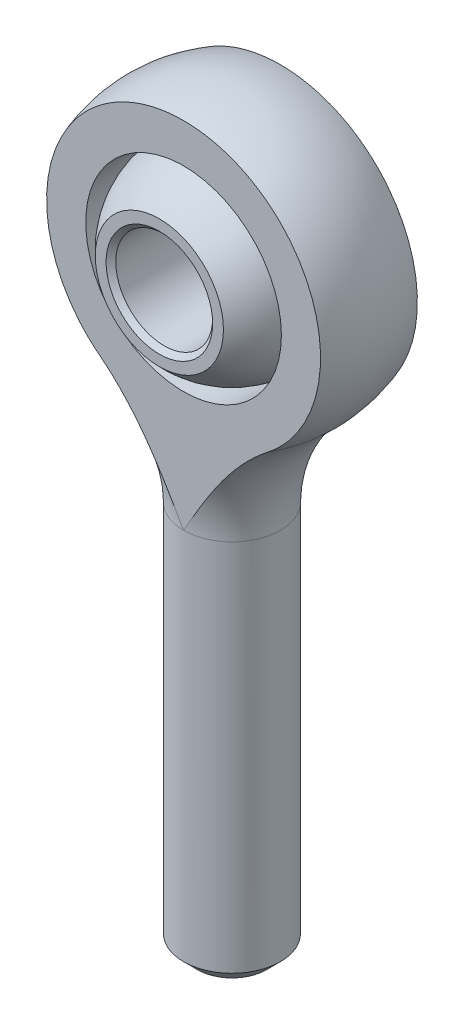
SolidWorks part; units mm, degrees
material "Cast Carbon Steel"
ref_plane "Front" through (0, 0, 0) normal (0, 0, 1) x (1, 0, 0)
ref_plane "Top" through (0, 0, 0) normal (0, 1, 0) x (1, 0, 0)
ref_plane "Right" through (0, 0, 0) normal (1, 0, 0) x (0, 0, -1)
sketch "Sketch1" plane through (0, 0, 0) normal (0, 0, 1) x (1, 0, 0)
  line L0 (0, 0) -> (0, -25.4)
  line L1 (0, -25.4) -> (3.175, -25.4)
  line L2 (3.175, -25.4) -> (3.175, 0)
  line L3 (3.175, 0) -> (0, 0)
  line L5 (0, 23.8125) -> (0, 0) construction
  line L6 (0, 23.8125) -> (9.525, 23.8125) construction
  line L7 (9.525, 23.8125) -> (9.525, 14.2875) construction
  line L8 (-3.175, -25.4) -> (-3.175, 0) construction
  arc A0 (6.3827, 7.2174) -> (0, 23.8125) centre (0, 14.2875) ccw construction
  circle A1 centre (0, 14.2875) radius 3.175 construction
  circle A2 centre (0, 14.2875) radius 6.35 construction
  circle A3 centre (0, 14.2875) radius 6.4135 construction
  arc A4 (3.175, 0) -> (6.3827, 7.2174) centre (12.8984, 0) cw construction
  dimension "A" = 6.35
  dimension "Ball Dia" = 12.7
  dimension "B" = 19.05
  dimension "D1" = 12.827
  dimension "D" = 39.6875
  dimension "E" = 25.4
  dimension "Thread Dia" = 6.35
revolve "Revolve1" add sketch "Sketch1" angle 360 about L5
chamfer "Chamfer2" distance 0.9068 angle 45 1 edges at (-3.175, -25.4, 0)
sketch "Sketch12" plane through (0, -25.4, 0) normal (0, -1, 0) x (1, 0, 0)
  circle A1 centre (0, 0) radius 2.2682
  circle A2 centre (0, 0) radius 2.2682
  dimension "D1" = 0
curve "Helix/Spiral1" [suppressed] pitch 0.9068 height 30.48 turns 33.6134
sketch "Sketch13" plane through (0, 0, 0) normal (0, 0, 1) x (1, 0, 0)
  line L0 (3.175, -25.4) -> (3.175, -26.1934)
  line L1 (3.175, -26.1934) -> (2.586, -25.8534)
  line L2 (2.586, -25.8534) -> (2.586, -25.74)
  line L3 (2.586, -25.74) -> (3.175, -25.4)
  line L4 (2.8805, -25.57) -> (2.8805, -26.0234) construction
  dimension "D1" = 60
  dimension "D2" = 0.1133
  dimension "D3" = 0.4534
sweep "Cut-Sweep2" [suppressed] cut profiles "Sketch13" path "Helix/Spiral1"
sketch "Sketch4" plane through (0, 0, 0) normal (0, 0, 1) x (1, 0, 0)
  line L0 (3.175, 0) -> (0, 0) construction
  line L2 (0, 23.8125) -> (0, 0) construction
  line L3 (3.175, 0) -> (0, 0)
  line L5 (0, 23.8125) -> (0, 0)
  line L6 (0, 23.8125) -> (0, 26.3525) construction
  arc A0 (6.3827, 7.2174) -> (0, 23.8125) centre (0, 14.2875) ccw construction
  arc A1 (6.3827, 7.2174) -> (0, 23.8125) centre (0, 14.2875) ccw
  arc A2 (6.3827, 7.2174) -> (3.175, 0) centre (12.8984, 0) ccw construction
  arc A3 (6.3827, 7.2174) -> (3.175, 0) centre (12.8984, 0) ccw
  dimension "D1" = 2.54
revolve "Revolve2" add sketch "Sketch4" angle 360 about L6
sketch "Sketch5" plane through (0, 0, 0) normal (1, 0, 0) x (0, 0, -1)
  line L0 (3.175, 23.8125) -> (9.525, 23.8125)
  line L1 (-3.175, 23.8125) -> (3.175, 23.8125) construction
  line L2 (-3.175, 23.8125) -> (-3.175, 1.27)
  line L3 (-3.175, 0) -> (3.175, 0) construction
  line L4 (3.175, 23.8125) -> (3.175, 1.27)
  line L5 (9.525, 23.8125) -> (9.525, 0)
  line L6 (9.525, 0) -> (3.175, 0)
  line L7 (-3.175, 0) -> (-9.525, 0)
  line L8 (-9.525, 0) -> (-9.525, 23.8125)
  line L9 (-9.525, 23.8125) -> (-3.175, 23.8125)
  line L10 (3.175, 0) -> (3.175, 1.27)
  line L11 (-3.175, 0) -> (-3.175, 1.27)
  line L12 (-3.175, 1.27) -> (3.175, 1.27) construction
  line L13 (0, 0) -> (0, 1.27) construction
  arc A0 (6.3827, 7.2174) -> (-6.3827, 7.2174) centre (0, 14.2875) ccw construction
  dimension "F" = 6.35
  dimension "D2" = 1.27
  dimension "D1" = 6.35
extrude "Cut-Extrude1" cut sketch "Sketch5" against normal through all and the other way through all
sketch "Sketch6" plane through (0, 0, 0) normal (0, 0, 1) x (1, 0, 0)
  circle A0 centre (0, 14.2875) radius 6.4135 construction
  circle A1 centre (0, 14.2875) radius 6.4135
extrude "Cut-Extrude2" cut sketch "Sketch6" against normal through all and the other way through all
sketch "Sketch7" plane through (0, 0, 0) normal (0, 0, 1) x (1, 0, 0)
  line L0 (0, 20.6375) -> (0, 7.9375)
  line L1 (0, 23.8125) -> (0, 0) construction
  line L2 (0, 0) -> (0, 7.9375) construction
  arc A0 (0, 7.9375) -> (0, 20.6375) centre (0, 14.2875) ccw
  circle A1 centre (0, 14.2875) radius 6.35 construction
revolve "Revolve3" add sketch "Sketch7" angle 360 about L2
sketch "Sketch8" plane through (0, 0, 0) normal (1, 0, 0) x (0, 0, -1)
  line L0 (-3.175, 23.8125) -> (3.175, 23.8125) construction
  line L1 (-4.7625, 23.8125) -> (4.7625, 23.8125) construction
  line L2 (-4.7625, 23.8125) -> (-4.7625, 0)
  line L3 (-4.7625, 0) -> (4.7625, 0) construction
  line L4 (4.7625, 23.8125) -> (4.7625, 0)
  line L5 (4.7625, 23.8125) -> (9.525, 23.8125)
  line L6 (9.525, 23.8125) -> (9.525, 0)
  line L7 (9.525, 0) -> (4.7625, 0)
  line L8 (-4.7625, 0) -> (-9.525, 0)
  line L9 (-9.525, 0) -> (-9.525, 23.8125)
  line L10 (-9.525, 23.8125) -> (-4.7625, 23.8125)
  dimension "C" = 9.525
extrude "Cut-Extrude3" cut sketch "Sketch8" against normal through all and the other way through all
sketch "Sketch10" plane through (0, 0, 0) normal (0, 0, 1) x (1, 0, 0)
  circle A0 centre (0, 14.2875) radius 3.175 construction
  circle A1 centre (0, 14.2875) radius 3.175
extrude "Cut-Extrude4" cut sketch "Sketch10" against normal through all and the other way through all
chamfer "Chamfer1" distance 0.3175 angle 45 2 edges at (3.175, 14.2875, -4.7625) (3.175, 14.2875, 4.7625)
sketch "Sketch14" [suppressed] plane through (0, 0, 0) normal (1, 0, 0) x (0, 0, -1)
  line L0 (2.4016, 13.0969) -> (-2.4016, 13.0969) construction
  line L1 (3.9688, 13.0969) -> (-3.9688, 13.0969)
  line L2 (-3.9688, 13.0969) -> (-3.9688, 13.6049)
  line L3 (-2.6, 13.5616) -> (2.6, 13.5616)
  line L4 (-2.6, 13.5616) -> (-2.6, 8.6634) construction
  line L5 (3.9688, 13.6049) -> (3.9688, 13.0969)
  arc A0 (-3.9688, 13.6049) -> (-2.6, 13.5616) centre (-3.9688, -8.0834) cw
  arc A1 (2.6, 13.5616) -> (3.9688, 13.6049) centre (3.9688, -8.0834) cw
  point P11 (0, 13.0969)
  dimension "D1" = 7.9375
  dimension "D2" = 0.508
revolve "Revolve4" [suppressed] add sketch "Sketch14" angle 360
fillet "Fillet1" [suppressed] radius 0.508
sketch "Sketch11" plane through (0, 0, 0) normal (1, 0, 0) x (0, 0, -1)
  line L0 (0, 14.2875) -> (-4.7625, 15.4309) construction
  line L1 (3.175, 14.2875) -> (-3.175, 14.2875) construction
  line L2 (0, 14.2875) -> (-4.7625, 13.1441) construction
  line L3 (0, 23.8125) -> (0, 0) construction
  line L4 (-4.7625, 23.8125) -> (-4.7625, 0) construction
  line L5 (0, 14.2875) -> (0.0074, 14.2875) construction
  dimension "Swivel" = 27
sketch "Sketch15" plane through (0, 0, 0) normal (1, 0, 0) x (0, 0, -1)
  line L0 (-4.445, 11.1125) -> (4.445, 11.1125) construction
  line L1 (4.445, 17.4625) -> (-4.445, 17.4625) construction
  line L2 (-4.445, 11.1125) -> (4.445, 11.1125) construction
  line L3 (4.445, 17.4625) -> (-4.445, 17.4625) construction
  line L4 (-3.175, 23.2678) -> (-3.175, 7.2174) construction
  line L5 (3.175, 7.2174) -> (3.175, 23.2678) construction
  arc A0 (-4.7625, 10.0874) -> (4.7625, 10.0874) centre (0, 14.2875) ccw construction
  arc A1 (4.7625, 18.4876) -> (-4.7625, 18.4876) centre (0, 14.2875) ccw construction
  arc A2 (-3.175, 8.7882) -> (3.175, 8.7882) centre (0, 14.2875) ccw construction
  arc A3 (3.175, 19.7868) -> (-3.175, 19.7868) centre (0, 14.2875) ccw construction
equation "\"D1@Sketch1\"=\"Ball Dia@Sketch1\"*1.01"
equation "\"D1@Chamfer1\"=\"A@Sketch1\"/20"
equation "\"D1@Sketch5\"=\"Thread Dia@Sketch1\""
equation "\"D2@Sketch5\"=\"F@Sketch5\"/5"
equation "\"D3@Helix/Spiral1\" = \"E@Sketch1\" + .2"
equation "\"D2@Sketch13\" = \"D4@Helix/Spiral1\" * .125"
equation "\"D3@Sketch13\" = \"D4@Helix/Spiral1\" * .5"
equation "\"D1@Chamfer2\" = \"D4@Helix/Spiral1\" * 1"
